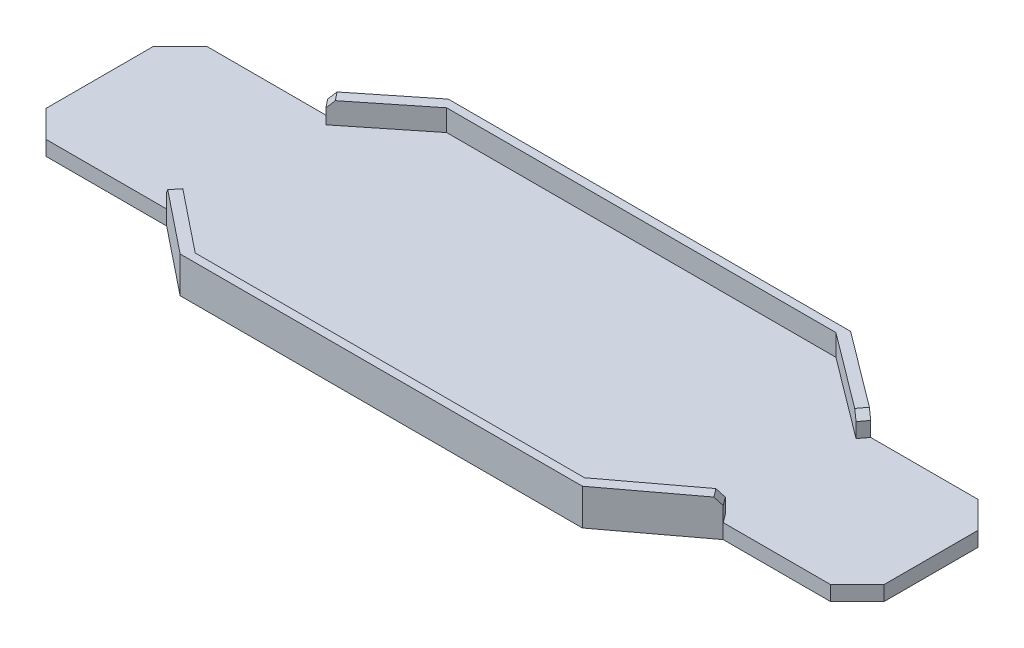
SolidWorks part; units mm, degrees
ref_plane "Front Plane" through (0, 0, 0) normal (0, 0, 1) x (1, 0, 0)
ref_plane "Top Plane" through (0, 0, 0) normal (0, 1, 0) x (1, 0, 0)
ref_plane "Right Plane" through (0, 0, 0) normal (1, 0, 0) x (0, 0, -1)
sketch "Sketch1" plane through (0, 0, 0) normal (0, 1, 0) x (1, 0, 0)
  line L0 (-235.1499, 0) -> (235.1499, 0) construction
  line L1 (0, 0) -> (0, 52596.8311) construction
  line L2 (-100, 30) -> (-75, 50)
  line L3 (-75, 50) -> (75, 50)
  line L4 (-100, 30) -> (-155, 30)
  line L5 (-155, 30) -> (-155, -30)
  line L6 (-75, -50) -> (75, -50)
  line L7 (-100, -30) -> (-75, -50)
  line L8 (-100, -30) -> (-155, -30)
  line L9 (75, 50) -> (105, 27.5)
  line L10 (105, 27.5) -> (155, 27.5)
  line L11 (155, 27.5) -> (155, -27.5)
  line L12 (105, -27.5) -> (155, -27.5)
  line L13 (75, -50) -> (105, -27.5)
  point P3 (0, 0)
  point P10 (-87.5, 40)
  point P15 (-87.5, -40)
  point P18 (-155, 0)
  point P19 (0, -50)
  point P20 (0, 50)
  point P23 (155, 0)
  dimension "D1" = 50
  dimension "D2" = 60
  dimension "D3" = 25
  dimension "D4" = 55
  dimension "D5" = 150
  dimension "D6" = 50
  dimension "D7" = 55
  dimension "D8" = 30
extrude "Boss-Extrude1" add sketch "Sketch1" along normal blind 5.5
sketch "Sketch3" plane through (0, 5.5, 0) normal (0, 1, 0) x (1, 0, 0)
  line L0 (0, 0) -> (50000, 0) construction
  line L1 (0, 0) -> (0, 50000) construction
  line L2 (0, 50) -> (-75, 50)
  line L3 (75, 50) -> (-75, 50) construction
  line L4 (-75, 50) -> (-100, 30)
  line L5 (-100, 30) -> (-97.5012, 26.8765)
  line L6 (-97.5012, 26.8765) -> (-72.5012, 46.8765)
  line L7 (-72.5012, 46.8765) -> (0, 46.8765)
  line L8 (-75, 50) -> (-72.5012, 46.8765) construction
  line L9 (0, 50) -> (75, 50)
  line L10 (75, 50) -> (105, 27.5)
  line L11 (105, 27.5) -> (102.6574, 24.3765)
  line L12 (102.6574, 24.3765) -> (72.6574, 46.8765)
  line L13 (72.6574, 46.8765) -> (0, 46.8765)
  line L14 (72.6574, 46.8765) -> (75, 50) construction
  line L15 (72.6574, -46.8765) -> (75, -50) construction
  line L16 (-75, -50) -> (-72.5012, -46.8765) construction
  line L17 (72.6574, -46.8765) -> (0, -46.8765)
  line L18 (102.6574, -24.3765) -> (72.6574, -46.8765)
  line L19 (105, -27.5) -> (102.6574, -24.3765)
  line L20 (75, -50) -> (105, -27.5)
  line L21 (0, -50) -> (75, -50)
  line L22 (-72.5012, -46.8765) -> (0, -46.8765)
  line L23 (-97.5012, -26.8765) -> (-72.5012, -46.8765)
  line L24 (-100, -30) -> (-97.5012, -26.8765)
  line L25 (-75, -50) -> (-100, -30)
  line L26 (0, -50) -> (-75, -50)
  dimension "D1" = 4
extrude "Chassis-Walls1" add sketch "Sketch3" along normal blind 8
chamfer "Chamfer1" distance 10 angle 45 2 edges at (-155, 2.75, -30) (-155, 2.75, 30)
chamfer "Chamfer2" distance 10 angle 45 2 edges at (155, 2.75, -27.5) (155, 2.75, 27.5)
chamfer "Chamfer3" distance 2.5 angle 45 4 edges at (-98.7506, 13.5, -28.4383) (-98.7506, 13.5, 28.4383) (103.8287, 13.5, 25.9383) (103.8287, 13.5, -25.9383)
sketch "Sketch4" plane through (0, 5.5, 0) normal (0, 1, 0) x (1, 0, 0)
  line L0 (145, 27.5) -> (105, 27.5) construction
  line L1 (125, 27.5) -> (125, -27.5) construction
  line L2 (105, -27.5) -> (145, -27.5) construction
  line L3 (123.5, 27.5) -> (123.5, -27.5) construction
  line L4 (123.5, -27.5) -> (126.5, -27.5) construction
  line L5 (123.5, 27.5) -> (126.5, 27.5) construction
  line L6 (126.5, 27.5) -> (126.5, -27.5) construction
  line L7 (-122.5, 30) -> (-122.5, -30) construction
  line L8 (-100, 30) -> (-145, 30) construction
  line L9 (-145, -30) -> (-100, -30) construction
  line L10 (-121, 30) -> (-124, 30) construction
  line L11 (-124, 30) -> (-124, -30) construction
  line L12 (-124, -30) -> (-121, -30) construction
  line L13 (-121, 30) -> (-121, -30) construction
  line L14 (0, 0) -> (50000, 0) construction
  line L15 (0, 0) -> (0, 50000) construction
  line L16 (67.5, 20) -> (-67.5, 20)
  line L17 (-67.5, 20) -> (-67.5, -20)
  line L18 (67.5, 20) -> (67.5, -20)
  line L19 (67.5, -20) -> (-67.5, -20)
  line L21 (-131.5, 22.5) -> (-106.5, 22.5)
  line L22 (-131.5, 22.5) -> (-131.5, -22.5)
  line L23 (-131.5, -22.5) -> (-106.5, -22.5)
  line L24 (-106.5, 22.5) -> (-106.5, -22.5)
  line L25 (-131.5, 22.5) -> (-106.5, -22.5) construction
  line L26 (-131.5, -22.5) -> (-106.5, 22.5) construction
  line L27 (107.5, 7) -> (142.5, 7)
  line L28 (107.5, 7) -> (107.5, -7)
  line L29 (107.5, -7) -> (142.5, -7)
  line L30 (142.5, 7) -> (142.5, -7)
  line L31 (107.5, 7) -> (142.5, -7) construction
  line L32 (107.5, -7) -> (142.5, 7) construction
  circle A0 centre (-142.5, 15) radius 2
  circle A1 centre (-97.5, 15) radius 2
  circle A2 centre (-97.5, -15) radius 2
  circle A3 centre (-142.5, -15) radius 2
  circle A4 centre (138, 15) radius 2
  circle A5 centre (113, 15) radius 2
  circle A6 centre (113, -15) radius 2
  circle A7 centre (138, -15) radius 2
  point P28 (0, -20)
  point P30 (0, 20)
  point P31 (67.5, 0)
  point P32 (-67.5, 0)
  point P49 (-119, 0)
  point P54 (125, 0)
  dimension "D7" = 4
  dimension "D8" = 4
  dimension "D11" = 4
  dimension "D16" = 4
  dimension "D1" = 3
  dimension "D2" = 3
  dimension "D3" = 40
  dimension "D4" = 135
  dimension "D5" = 20
  dimension "D6" = 15
  dimension "D9" = 15
  dimension "D10" = 25
  dimension "D12" = 15
  dimension "D13" = 15
  dimension "D14" = 12
  dimension "D15" = 13
  dimension "D17" = 25
  dimension "D18" = 45
  dimension "D19" = 16
  dimension "D20" = 14
  dimension "D21" = 35
split line "Split Line1" [suppressed]
